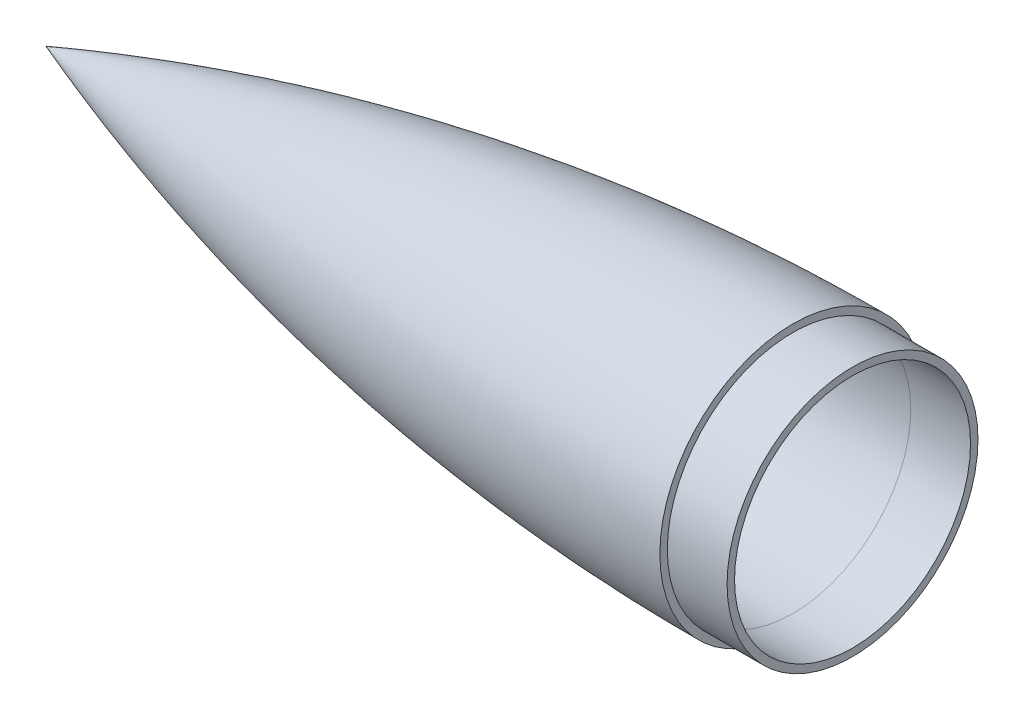
SolidWorks part; units mm, degrees
material "Alliage 1060"
ref_plane "Plan de face" through (0, 0, 0) normal (0, 0, 1) x (1, 0, 0)
ref_plane "Plan de dessus" through (0, 0, 0) normal (0, 1, 0) x (1, 0, 0)
ref_plane "Plan de droite" through (0, 0, 0) normal (1, 0, 0) x (0, 0, -1)
sketch "Esquisse1" plane through (0, 0, 0) normal (0, 1, 0) x (1, 0, 0)
  line L0 (0, 0) -> (301.6119, 0) construction
  line L1 (250, 44.5) -> (250, 0)
  line L2 (250, 0) -> (0, 0) construction
  line L3 (250, 0) -> (0, 0)
  line L4 (-54.2063, 0) -> (320.9698, 0) construction
  spline S0 degree 4 poles (-23.7502, -9.2088) (-23.3799, -9.0577) (-22.6355, -8.7547) (-21.157, -8.1549) (-18.9186, -7.2551) (-16.3279, -6.2241) (-13.3349, -5.0492) (-10.3972, -3.9098) (-7.7516, -2.8983) (-5.6094, -2.0868) (-3.6309, -1.3456) (-2.3941, -0.8836) (-0.4558, -0.1673) (0.4092, 0.1508) (2.3016, 0.8431) (3.4751, 1.2677) (5.0519, 1.8372) (6.3963, 2.3179) (7.8768, 2.8452) (9.2834, 3.342) (11.0887, 3.976) (13.2331, 4.722) (15.7521, 5.5887) (18.6271, 6.5642) (22.2303, 7.7702) (26.56, 9.1922) (31.6241, 10.8165) (37.4262, 12.6239) (43.2437, 14.3827) (49.0755, 16.0926) (56.3831, 18.1687) (65.1796, 20.5619) (74.0089, 22.8319) (82.8689, 24.9782) (91.7522, 27.0252) (100.6579, 28.9729) (111.0789, 31.0996) (121.5341, 33.0513) (130.5181, 34.5986) (138.0186, 35.8043) (144.0268, 36.7184) (151.5465, 37.7981) (159.0778, 38.7935) (166.6198, 39.7047) (175.6818, 40.6969) (183.2423, 41.4391) (190.8106, 42.0968) (197.6282, 42.6125) (202.1756, 42.9245) (205.9663, 43.1633) (209, 43.3416) (212.0337, 43.5072) (215.0692, 43.6601) (218.1036, 43.8002) (221.1412, 43.9276) (224.9341, 44.071) (229.4951, 44.2175) (233.6629, 44.3226) (237.4726, 44.3943) (240.4938, 44.4389) (242.4321, 44.4615) (244.2523, 44.4788) (246.2753, 44.4907) (247.5689, 44.4971) (249.5417, 44.5003) (250.4914, 44.5003) (252.8953, 44.4961) (254.9342, 44.4845) (257.8361, 44.4612) (260.8405, 44.4211) (264.0327, 44.3674) (267.1222, 44.3) (269.905, 44.229) (272.0457, 44.1653) (273.6288, 44.115) (274.4094, 44.0887) (274.803, 44.0753) (275.0002, 44.0685) knots 0 0 0 0 0 0.005239 0.010478 0.020956 0.031434 0.041913 0.052265 0.062618 0.067794 0.072971 0.078147 0.083323 0.088293 0.093262 0.098232 0.103201 0.108171 0.113141 0.11811 0.12308 0.133019 0.142958 0.152897 0.162836 0.182715 0.202593 0.222471 0.24235 0.262228 0.282106 0.321863 0.361619 0.381498 0.401376 0.441132 0.480889 0.520646 0.540524 0.560402 0.58028 0.600159 0.639915 0.659794 0.679672 0.719428 0.739307 0.759185 0.769124 0.779063 0.789003 0.798942 0.808881 0.81882 0.828759 0.838698 0.858577 0.878455 0.883424 0.888394 0.898333 0.903303 0.908272 0.913242 0.918211 0.923292 0.928372 0.938532 0.948693 0.958853 0.96914 0.979427 0.989713 0.994857 0.997428 1 1 1 1 1 construction
  spline S1 degree 4 poles (0, 0) (0.2976, 0.1094) (0.8969, 0.3292) (2.3016, 0.8431) (3.4751, 1.2677) (5.0519, 1.8372) (6.3963, 2.3179) (7.8768, 2.8452) (9.2834, 3.342) (11.0887, 3.976) (13.2331, 4.722) (15.7521, 5.5887) (18.6271, 6.5642) (22.2303, 7.7702) (26.56, 9.1922) (31.6241, 10.8165) (37.4262, 12.6239) (43.2437, 14.3827) (49.0755, 16.0926) (56.3831, 18.1687) (65.1796, 20.5619) (74.0089, 22.8319) (82.8689, 24.9782) (91.7522, 27.0252) (100.6579, 28.9729) (111.0789, 31.0996) (121.5341, 33.0513) (130.5181, 34.5986) (138.0186, 35.8043) (144.0268, 36.7184) (151.5465, 37.7981) (159.0778, 38.7935) (166.6198, 39.7047) (175.6818, 40.6969) (183.2423, 41.4391) (190.8106, 42.0968) (197.6282, 42.6125) (202.1756, 42.9245) (205.9663, 43.1633) (209, 43.3416) (212.0337, 43.5072) (215.0692, 43.6601) (218.1036, 43.8002) (221.1412, 43.9276) (224.9341, 44.071) (229.4951, 44.2175) (233.6629, 44.3226) (237.4726, 44.3943) (240.4938, 44.4389) (242.4321, 44.4615) (244.2523, 44.4788) (246.2753, 44.4907) (247.5689, 44.4971) (249.0403, 44.4995) (249.6829, 44.5) (250, 44.5) knots 0.083323 0.083323 0.083323 0.083323 0.083323 0.088293 0.093262 0.098232 0.103201 0.108171 0.113141 0.11811 0.12308 0.133019 0.142958 0.152897 0.162836 0.182715 0.202593 0.222471 0.24235 0.262228 0.282106 0.321863 0.361619 0.381498 0.401376 0.441132 0.480889 0.520646 0.540524 0.560402 0.58028 0.600159 0.639915 0.659794 0.679672 0.719428 0.739307 0.759185 0.769124 0.779063 0.789003 0.798942 0.808881 0.81882 0.828759 0.838698 0.858577 0.878455 0.883424 0.888394 0.898333 0.903303 0.908272 0.913242 0.918211 0.918211 0.918211 0.918211 0.918211
  dimension "D1" = 250
  dimension "D2" = 44.5
revolve "Révolution1" add sketch "Esquisse1" angle 360 about L3
shell "Coque4" thickness 5 removed face at (250, 0, -44.5)
sketch "Esquisse2" plane through (250, 0, 0) normal (1, 0, 0) x (0, 0, -1)
sketch "Esquisse3" plane through (250, 0, 0) normal (1, 0, 0) x (0, 0, -1)
  circle A0 centre (0, 0) radius 39.5
  circle A1 centre (0, 0) radius 42
  dimension "D1" = 84
  dimension "D2" = 79
extrude "Boss.-Extru.1" add sketch "Esquisse3" along normal blind 20
